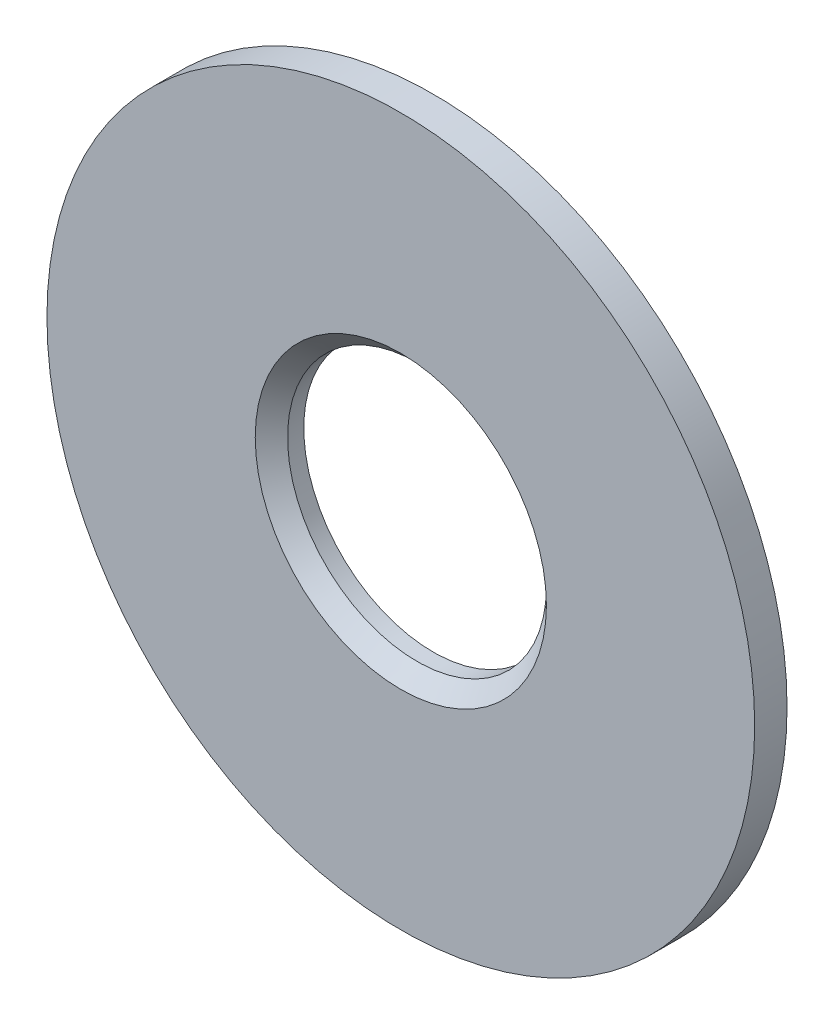
SolidWorks part; units mm, degrees
ref_plane "Plano frontal" through (0, 0, 0) normal (0, 0, 1) x (1, 0, 0)
ref_plane "Plano superior" through (0, 0, 0) normal (0, 1, 0) x (1, 0, 0)
ref_plane "Plano direito" through (0, 0, 0) normal (1, 0, 0) x (0, 0, -1)
sketch "Esboço2" plane through (0, 0, 0) normal (0, 0, 1) x (1, 0, 0)
  circle A0 centre (0, 0) radius 43.75
  circle A1 centre (0, 0) radius 16
  dimension "D1" = 32
  dimension "D2" = 87.5
extrude "Ressalto-extrusão1" add sketch "Esboço2" along normal blind 4
ref_axis "Eixo1" through (0, 0, 4) along (0, 0, -1)
chamfer "Chanfro2" distance 2 angle 45 1 edges at (16, 0, 4)
